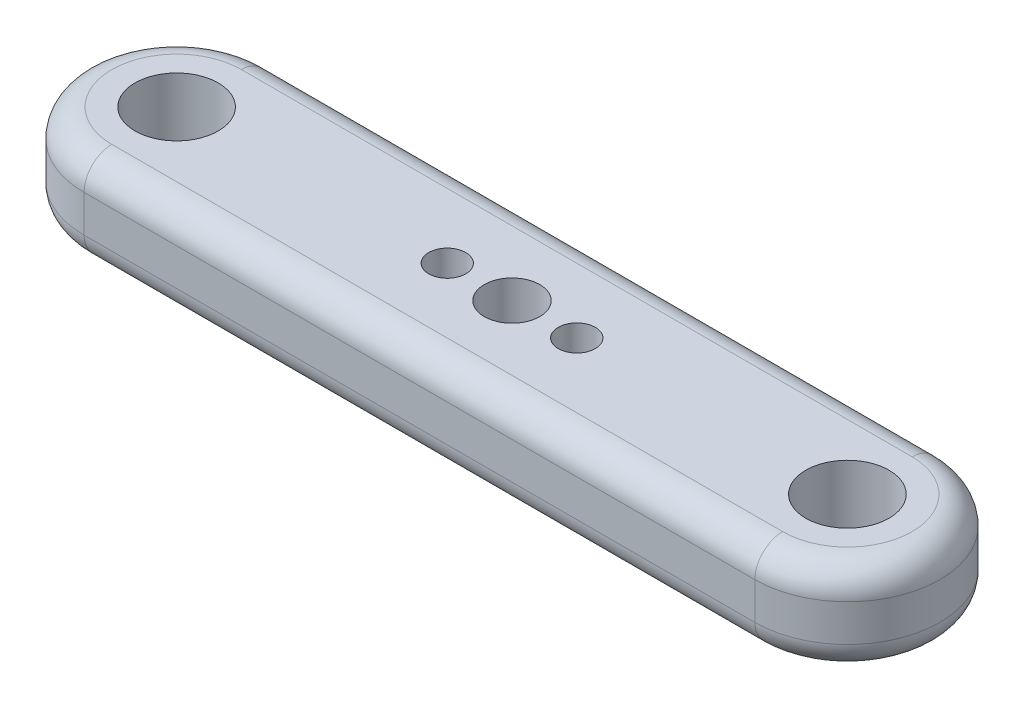
SolidWorks part; units mm, degrees
ref_plane "Front Plane" through (0, 0, 0) normal (0, 0, 1) x (1, 0, 0)
ref_plane "Top Plane" through (0, 0, 0) normal (0, 1, 0) x (1, 0, 0)
ref_plane "Right Plane" through (0, 0, 0) normal (1, 0, 0) x (0, 0, -1)
sketch "Sketch2" plane through (0, 0, 0) normal (0, 1, 0) x (1, 0, 0)
  line L4 (-36.25, 10) -> (36.25, 10)
  line L10 (36.25, -10) -> (-36.25, -10)
  arc A1 (0, -5) -> (0, 5) centre (0, 0) ccw
  circle A5 centre (0, 0) radius 5
  circle A6 centre (-36.25, 0) radius 5
  circle A7 centre (36.25, 0) radius 5
  arc A8 (-36.25, 10) -> (-36.25, -10) centre (-36.25, 0) ccw
  arc A9 (36.25, -10) -> (36.25, 10) centre (36.25, 0) ccw
  circle A10 centre (-36.25, 0) radius 10 construction
  circle A11 centre (36.25, 0) radius 10 construction
  point P3 (-19.375, 0)
  dimension "D1" = 5
  dimension "D2" = 5
extrude "Boss-Extrude1" add sketch "Sketch2" along normal blind 10 contours L10 A9 L4 A8 A5 A1 A6 A7 region at (0, 0, -9.0536)
fillet "Fillet1" radius 3 8 edges at (-46.25, 0, 0) (0, 0, 10) (46.25, 0, 0) (-46.25, 10, 0) (0, 10, 10) (46.25, 10, 0) (0, 0, -10) (0, 10, -10)
sketch "Sketch3" plane through (0, 10, 0) normal (0, 1, 0) x (1, 0, 0)
  line L0 (0, 0) -> (-6.5, 0)
  line L1 (-6.5, 0) -> (7.6495, 0)
  circle A0 centre (0, 0) radius 5
  circle M5 centre (0, 0) radius 5
extrude "Boss-Extrude2" add sketch "Sketch3" against normal blind 10 contours L0 L1 M5 | L1 L0 M5 region at (0, 10, 2.1221) region at (0, 10, -2.1221)
sketch "Sketch4" plane through (0, 10, 0) normal (0, 1, 0) x (1, 0, 0)
  line L0 (0, 0) -> (-8.2, 0)
  line L1 (0, 0) -> (8.2, 0)
  circle A0 centre (-8.2, 0) radius 1.5
  circle A1 centre (8.2, 0) radius 1.5
sketch "Sketch5" plane through (0, 10, 0) normal (0, 1, 0) x (1, 0, 0)
  circle A0 centre (-36.25, 0) radius 4.5
  circle A1 centre (-36.25, 0) radius 5
  circle A2 centre (36.25, 0) radius 5
  circle A3 centre (36.25, 0) radius 4.5
extrude "Boss-Extrude3" add sketch "Sketch5" against normal up to surface (10 mm away) up to face at (0, 0, 0)
sketch "Sketch6" plane through (0, 10, 0) normal (0, 1, 0) x (1, 0, 0)
  line L0 (7, 0) -> (-7, 0)
  circle A1 centre (-7, 0) radius 2
  circle A2 centre (7, 0) radius 2
extrude "Cut-Extrude1" cut sketch "Sketch6" against normal blind 10 contours A1 | A2 region at (-8.9434, 10, 0) region at (7, 10, -1.9434)
sketch "Sketch7" plane through (0, 10, 0) normal (0, 1, 0) x (1, 0, 0)
  circle A0 centre (0, 0) radius 3
extrude "Cut-Extrude2" cut sketch "Sketch7" against normal blind 10
